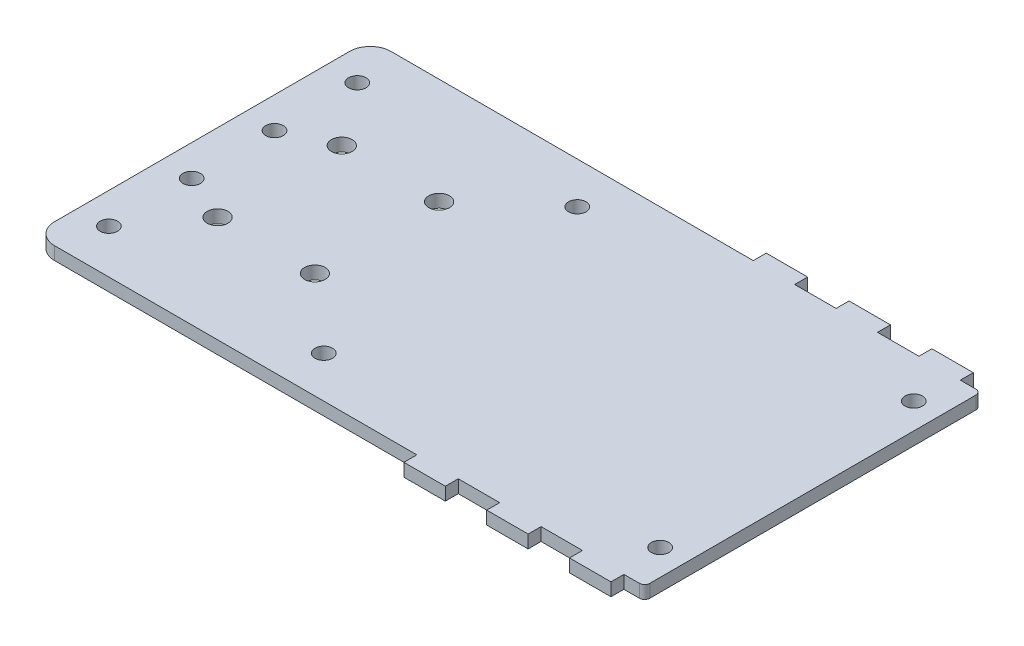
SolidWorks part; units mm, degrees
ref_plane "Front Plane" through (0, 0, 0) normal (0, 0, 1) x (1, 0, 0)
ref_plane "Top Plane" through (0, 0, 0) normal (0, 1, 0) x (1, 0, 0)
ref_plane "Right Plane" through (0, 0, 0) normal (1, 0, 0) x (0, 0, -1)
sketch "Sketch1" plane through (0, 0, 0) normal (0, 1, 0) x (1, 0, 0)
  line L0 (38.1, -41.275) -> (48.26, -41.275)
  line L1 (76.2, -41.275) -> (-76.2, -41.275)
  line L2 (76.2, -41.275) -> (76.2, 41.275)
  line L3 (76.2, 41.275) -> (-76.2, 41.275)
  line L4 (-76.2, -41.275) -> (-76.2, 41.275)
  line L5 (76.2, -41.275) -> (-76.2, 41.275) construction
  line L6 (76.2, 41.275) -> (-76.2, -41.275) construction
  line L7 (58.42, -41.275) -> (68.58, -41.275)
  line L8 (58.42, -41.275) -> (58.42, -44.45)
  line L9 (58.42, -44.45) -> (68.58, -44.45)
  line L10 (68.58, -41.275) -> (68.58, -44.45)
  line L11 (38.1, -41.275) -> (38.1, -44.45)
  line L12 (38.1, -44.45) -> (48.26, -44.45)
  line L13 (48.26, -41.275) -> (48.26, -44.45)
  line L14 (17.78, -41.275) -> (27.94, -41.275)
  line L15 (17.78, -41.275) -> (17.78, -44.45)
  line L16 (17.78, -44.45) -> (27.94, -44.45)
  line L17 (27.94, -41.275) -> (27.94, -44.45)
  line L18 (58.42, 44.45) -> (68.58, 44.45)
  line L19 (58.42, 44.45) -> (58.42, 41.275)
  line L20 (58.42, 41.275) -> (68.58, 41.275)
  line L21 (68.58, 44.45) -> (68.58, 41.275)
  line L22 (38.1, 44.45) -> (48.26, 44.45)
  line L23 (38.1, 44.45) -> (38.1, 41.275)
  line L24 (38.1, 41.275) -> (48.26, 41.275)
  line L25 (48.26, 44.45) -> (48.26, 41.275)
  line L26 (17.78, 44.45) -> (27.94, 44.45)
  line L27 (17.78, 44.45) -> (17.78, 41.275)
  line L28 (17.78, 41.275) -> (27.94, 41.275)
  line L29 (27.94, 44.45) -> (27.94, 41.275)
  line L30 (58.42, -41.275) -> (38.1, -41.275) construction
  point P0 (0, 0)
  dimension "D1" = 3.175
  dimension "D2" = 10.16
  dimension "D5" = 20.32
  dimension "D6" = 82.55
  dimension "D7" = 152.4
  dimension "D8" = 7.62
  dimension "D3" = 3
  dimension "D4" = 2
extrude "Main Extrude" add sketch "Sketch1" along normal blind 3.175 contours L17 L1 L15 L16 | L4 L1 L0 L2 L3 | L13 L0 L11 L12 | L29 L26 L27 L3 | L10 L9 L8 L7 | L18 L21 L20 L19 | L22 L25 L24 L23 region at (0, 0, 0) region at (43.18, 0, 42.8625) region at (22.86, 0, 42.8625) region at (22.86, 0, -42.8625)
sketch "Sketch2" plane through (0, 3.175, 0) normal (0, 1, 0) x (1, 0, 0)
  line L0 (-57.15, 15.24) -> (-57.15, -15.24) construction
  line L1 (-57.15, 0) -> (-76.2, 0) construction
  line L2 (-76.2, -41.275) -> (-76.2, 41.275) construction
  circle A0 centre (-57.15, 15.24) radius 2.54
  circle A1 centre (-33.274, 15.24) radius 2.54
  circle A2 centre (-33.274, -15.24) radius 2.54
  circle A3 centre (-57.15, -15.24) radius 2.54
  dimension "D4" = 23.876
  dimension "D5" = 5.08
  dimension "D3" = 30.48
  dimension "D6" = 19.05
  dimension "D1" = 2
  dimension "D2" = 2
extrude "Caster Mounting Holes" cut sketch "Sketch2" against normal through all
sketch "Sketch3" plane through (0, 3.175, 0) normal (0, 1, 0) x (1, 0, 0)
  line L0 (76.2, -41.275) -> (76.2, 41.275) construction
  line L1 (73.66, 41.275) -> (76.2, 41.275)
  line L2 (73.66, 41.275) -> (73.66, -41.275)
  line L3 (73.66, -41.275) -> (76.2, -41.275)
  line L4 (76.2, 41.275) -> (76.2, -41.275)
  dimension "D1" = 2.54
extrude "Remove Uneven Back Edge" cut sketch "Sketch3" against normal through all
sketch "Sketch5" plane through (0, 3.175, 0) normal (0, 1, 0) x (1, 0, 0)
  line L0 (-21.59, 41.275) -> (73.66, -41.275) construction
  line L1 (-21.59, 41.275) -> (73.66, 41.275) construction
  line L2 (-21.59, 41.275) -> (-21.59, -41.275) construction
  line L3 (-21.59, -41.275) -> (73.66, -41.275) construction
  line L4 (73.66, 41.275) -> (73.66, -41.275) construction
  line L5 (73.66, 41.275) -> (-21.59, -41.275) construction
  line L7 (67.31, -31.115) -> (-15.24, -31.115) construction
  line L8 (67.31, -31.115) -> (67.31, 31.115) construction
  line L9 (67.31, 31.115) -> (-15.24, 31.115) construction
  line L10 (-15.24, -31.115) -> (-15.24, 31.115) construction
  line L11 (67.31, -31.115) -> (-15.24, 31.115) construction
  line L12 (67.31, 31.115) -> (-15.24, -31.115) construction
  circle A0 centre (-15.24, 31.115) radius 2.15
  circle A1 centre (67.31, 31.115) radius 2.15
  circle A2 centre (67.31, -31.115) radius 2.15
  circle A3 centre (-15.24, -31.115) radius 2.15
  point P4 (26.035, 0)
  point P10 (26.035, 0)
  dimension "D5" = 4.3
  dimension "D1" = 95.25
  dimension "D2" = 82.55
  dimension "D3" = 82.55
  dimension "D4" = 62.23
extrude "Standoff Holes" cut sketch "Sketch5" against normal through all
fillet "Fillet1" radius 5.08 2 edges at (-76.2, 1.5875, 41.275) (-76.2, 1.5875, -41.275)
fillet "Fillet2" radius 1.27 1 edges at (73.66, 1.5875, 41.275)
fillet "Fillet3" radius 1.27 1 edges at (73.66, 1.5875, -41.275)
sketch "Sketch9" plane through (0, 3.175, 0) normal (0, 1, 0) x (1, 0, 0)
  line L0 (-76.2, -36.195) -> (-76.2, 36.195) construction
  line L1 (-68.58, -30.48) -> (-68.58, -41.275) construction
  line L2 (17.78, -41.275) -> (-71.12, -41.275) construction
  line L3 (-68.58, 30.48) -> (-68.58, 41.275) construction
  line L4 (17.78, 41.275) -> (-71.12, 41.275) construction
  circle A0 centre (-68.58, -30.48) radius 2.15
  circle A1 centre (-68.58, -10.16) radius 2.15
  circle A2 centre (-68.58, 10.16) radius 2.15
  circle A3 centre (-68.58, 30.48) radius 2.15
  dimension "D1" = 7.62
  dimension "D2" = 4.3
  dimension "D3" = 4
extrude "Front Mounting Holes" cut sketch "Sketch9" against normal through all
sketch "Sketch7" plane through (0, 3.175, 0) normal (0, 1, 0) x (1, 0, 0)
  line L544 (73.7362, -40.005) -> (73.7362, 40.005)
  line L545 (72.39, 41.3512) -> (68.6562, 41.3512)
  line L546 (68.6562, 41.3512) -> (68.6562, 44.5262)
  line L547 (68.6562, 44.5262) -> (58.3438, 44.5262)
  line L548 (58.3438, 44.5262) -> (58.3438, 41.3512)
  line L549 (58.3438, 41.3512) -> (48.3362, 41.3512)
  line L550 (48.3362, 41.3512) -> (48.3362, 44.5262)
  line L551 (48.3362, 44.5262) -> (38.0238, 44.5262)
  line L552 (38.0238, 44.5262) -> (38.0238, 41.3512)
  line L553 (38.0238, 41.3512) -> (28.0162, 41.3512)
  line L554 (28.0162, 41.3512) -> (28.0162, 44.5262)
  line L555 (28.0162, 44.5262) -> (17.7038, 44.5262)
  line L556 (17.7038, 44.5262) -> (17.7038, 41.3512)
  line L557 (17.7038, 41.3512) -> (-71.12, 41.3512)
  line L558 (-76.2762, 36.195) -> (-76.2762, -36.195)
  line L559 (-71.12, -41.3512) -> (17.7038, -41.3512)
  line L560 (17.7038, -41.3512) -> (17.7038, -44.5262)
  line L561 (17.7038, -44.5262) -> (28.0162, -44.5262)
  line L562 (28.0162, -44.5262) -> (28.0162, -41.3512)
  line L563 (28.0162, -41.3512) -> (38.0238, -41.3512)
  line L564 (38.0238, -41.3512) -> (38.0238, -44.5262)
  line L565 (38.0238, -44.5262) -> (48.3362, -44.5262)
  line L566 (48.3362, -44.5262) -> (48.3362, -41.3512)
  line L567 (48.3362, -41.3512) -> (58.3438, -41.3512)
  line L568 (58.3438, -41.3512) -> (58.3438, -44.5262)
  line L569 (58.3438, -44.5262) -> (68.6562, -44.5262)
  line L570 (68.6562, -44.5262) -> (68.6562, -41.3512)
  line L571 (68.6562, -41.3512) -> (72.39, -41.3512)
  line L572 (73.7362, -40.005) -> (73.7362, 40.005)
  line L573 (72.39, 41.3512) -> (68.6562, 41.3512)
  line L574 (68.6562, 41.3512) -> (68.6562, 44.5262)
  line L575 (68.6562, 44.5262) -> (58.3438, 44.5262)
  line L576 (58.3438, 44.5262) -> (58.3438, 41.3512)
  line L577 (58.3438, 41.3512) -> (48.3362, 41.3512)
  line L578 (48.3362, 41.3512) -> (48.3362, 44.5262)
  line L579 (48.3362, 44.5262) -> (38.0238, 44.5262)
  line L580 (38.0238, 44.5262) -> (38.0238, 41.3512)
  line L581 (38.0238, 41.3512) -> (28.0162, 41.3512)
  line L582 (28.0162, 41.3512) -> (28.0162, 44.5262)
  line L583 (28.0162, 44.5262) -> (17.7038, 44.5262)
  line L584 (17.7038, 44.5262) -> (17.7038, 41.3512)
  line L585 (17.7038, 41.3512) -> (-71.12, 41.3512)
  line L586 (-76.2762, 36.195) -> (-76.2762, -36.195)
  line L587 (-71.12, -41.3512) -> (17.7038, -41.3512)
  line L588 (17.7038, -41.3512) -> (17.7038, -44.5262)
  line L589 (17.7038, -44.5262) -> (28.0162, -44.5262)
  line L590 (28.0162, -44.5262) -> (28.0162, -41.3512)
  line L591 (28.0162, -41.3512) -> (38.0238, -41.3512)
  line L592 (38.0238, -41.3512) -> (38.0238, -44.5262)
  line L593 (38.0238, -44.5262) -> (48.3362, -44.5262)
  line L594 (48.3362, -44.5262) -> (48.3362, -41.3512)
  line L595 (48.3362, -41.3512) -> (58.3438, -41.3512)
  line L596 (58.3438, -41.3512) -> (58.3438, -44.5262)
  line L597 (58.3438, -44.5262) -> (68.6562, -44.5262)
  line L598 (68.6562, -44.5262) -> (68.6562, -41.3512)
  line L599 (68.6562, -41.3512) -> (72.39, -41.3512)
  circle A46 centre (67.31, -31.115) radius 2.0738
  circle A47 centre (67.31, -31.115) radius 2.0738
  arc A48 (72.39, -41.3512) -> (73.7362, -40.005) centre (72.39, -40.005) ccw
  arc A49 (73.7362, 40.005) -> (72.39, 41.3512) centre (72.39, 40.005) ccw
  arc A50 (-71.12, 41.3512) -> (-76.2762, 36.195) centre (-71.12, 36.195) ccw
  arc A51 (-76.2762, -36.195) -> (-71.12, -41.3512) centre (-71.12, -36.195) ccw
  arc A52 (72.39, -41.3512) -> (73.7362, -40.005) centre (72.39, -40.005) ccw
  arc A53 (73.7362, 40.005) -> (72.39, 41.3512) centre (72.39, 40.005) ccw
  arc A54 (-71.12, 41.3512) -> (-76.2762, 36.195) centre (-71.12, 36.195) ccw
  arc A55 (-76.2762, -36.195) -> (-71.12, -41.3512) centre (-71.12, -36.195) ccw
  circle A57 centre (67.31, 31.115) radius 2.0738
  circle A58 centre (67.31, 31.115) radius 2.0738
  circle A60 centre (-15.24, -31.115) radius 2.0738
  circle A61 centre (-15.24, -31.115) radius 2.0738
  circle A63 centre (-33.274, -15.24) radius 2.4638
  circle A64 centre (-33.274, -15.24) radius 2.4638
  circle A66 centre (-57.15, -15.24) radius 2.4638
  circle A67 centre (-57.15, -15.24) radius 2.4638
  circle A69 centre (-33.274, 15.24) radius 2.4638
  circle A70 centre (-33.274, 15.24) radius 2.4638
  circle A72 centre (-57.15, 15.24) radius 2.4638
  circle A73 centre (-57.15, 15.24) radius 2.4638
  circle A75 centre (-15.24, 31.115) radius 2.0738
  circle A76 centre (-15.24, 31.115) radius 2.0738
  circle A80 centre (-68.58, -30.48) radius 2.0738
  circle A81 centre (-68.58, -30.48) radius 2.0738
  circle A83 centre (-68.58, -10.16) radius 2.0738
  circle A84 centre (-68.58, -10.16) radius 2.0738
  circle A86 centre (-68.58, 10.16) radius 2.0738
  circle A87 centre (-68.58, 10.16) radius 2.0738
  circle A89 centre (-68.58, 30.48) radius 2.0738
  circle A90 centre (-68.58, 30.48) radius 2.0738
  dimension "D1" = 0.0762
  dimension "D2" = 0.0762
  dimension "D3" = 0.0762
  dimension "D4" = 0.0762
  dimension "D5" = 0.0762
  dimension "D6" = 0.0762
  dimension "D7" = 0.0762
  dimension "D8" = 0.0762
  dimension "D9" = 0.0762
  dimension "D10" = 0.0762
  dimension "D11" = 0.0762
  dimension "D12" = 0.0762
  dimension "D13" = 0.0762
